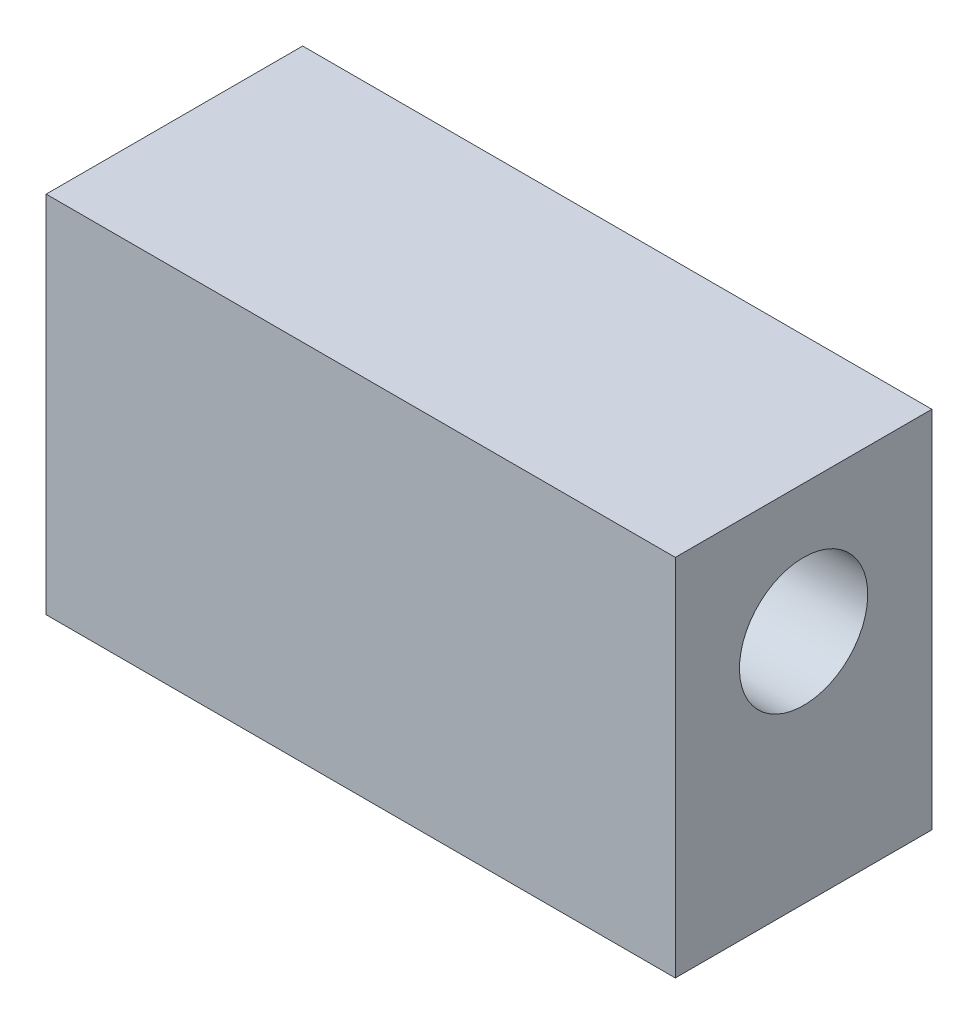
SolidWorks part; units mm, degrees
material "1060 Alloy"
ref_plane "Front" through (0, 0, 0) normal (0, 0, 1) x (1, 0, 0)
ref_plane "Top" through (0, 0, 0) normal (0, 1, 0) x (1, 0, 0)
ref_plane "Right" through (0, 0, 0) normal (1, 0, 0) x (0, 0, -1)
sketch "Sketch3" plane through (0, 0, 0) normal (0, 0, 1) x (1, 0, 0)
  line L0 (-0.127, -6.35) -> (30.1755, -6.35)
  line L1 (0, 0) -> (31.1484, 0)
  line L2 (0, 0) -> (0, -19.8376)
  line L3 (0, -19.8376) -> (31.1484, -19.8376)
  line L4 (31.1484, 0) -> (31.1484, -19.8376)
  line L5 (15.5742, -19.8376) -> (15.5742, 0) construction
  line L6 (15.5742, -6.35) -> (8.0621, -19.3614) construction
  line L15 (12.5496, -11.5887) -> (15.5742, -13.335) construction
  line L16 (15.5742, -6.35) -> (22.9274, -19.0862) construction
  circle A0 centre (15.5742, -6.35) radius 6.0492 construction
  point P14 (0, -6.35)
  point P17 (9.525, -6.35)
  point P19 (31.1484, -6.35)
  point P20 (7.7871, -19.8376)
  point P24 (23.3613, -19.8376)
  dimension "D2" = 6.35
  dimension "D6" = 3.4925
  dimension "D3" = 60
  dimension "D1" = 9.525
  dimension "D4" = 9.525
  dimension "D5" = 60
extrude "Boss-Extrude1" add sketch "Sketch3" along normal mid plane 12.7
sketch "Sketch4" plane through (0, 0, 0) normal (-1, 0, 0) x (0, 0, 1)
  circle A0 centre (0, -6.35) radius 3.175
  dimension "D1" = 6.35
extrude "Cut-Extrude1" cut sketch "Sketch4" against normal blind 9.525
ref_plane "Plane1" through (7.7871, -19.8376, 0) normal (-0.5, -0.866, 0) x (-0.866, 0.5, 0)
ref_plane "Mirror Plane" through (15.5742, 0, 0) normal (-1, 0, 0) x (0, 0, 1)
sketch "Sketch5" plane through (7.7871, -19.8376, 0) normal (-0.5, -0.866, 0) x (-0.866, 0.5, 0)
  circle A0 centre (0, 0) radius 3.175
  dimension "D1" = 6.35
extrude "Cut-Extrude5" cut sketch "Sketch5" against normal blind 9.525 and the other way up to next
sketch "Sketch6" plane through (0, 0, -6.35) normal (0, 0, -1) x (-1, 0, 0)
  circle A0 centre (-15.5742, -6.35) radius 3.175
  dimension "D1" = 6.35
extrude "Cut-Extrude6" cut sketch "Sketch6" against normal blind 9.525
mirror "Mirror1" about plane through (15.5742, 0, 0) normal (-1, 0, 0) of "Cut-Extrude1", "Cut-Extrude5"
sketch "Sketch8" plane through (31.1484, 0, 0) normal (1, 0, 0) x (0, 0, -1)
  line L0 (-6.35, -19.8376) -> (-6.35, 0) construction
  line L1 (-6.35, -18.034) -> (6.35, -18.034)
  line L2 (-6.35, -18.034) -> (-6.35, -19.8376)
  line L3 (-6.35, -19.8376) -> (6.35, -19.8376)
  line L4 (6.35, -18.034) -> (6.35, -19.8376)
  line L5 (-6.35, 0) -> (6.35, 0) construction
  dimension "D1" = 18.034
extrude "Cut-Extrude7" cut sketch "Sketch8" against normal through all
equation "\"truss_member_od\" = .25in"
equation "\"truss_member_id\"= 0in"
equation "\"truss_member_L1\" = 2.125in"
equation "\"connector_hole_depth\" = .375in"
equation "\"D1@Boss-Extrude1\"=\"truss_member_od\"*2"
equation "\"D6@Sketch3\"=\"truss_member_od\"/2*1.1"
equation "\"D1@Sketch4\"=\"truss_member_od\""
equation "\"D1@Cut-Extrude1\"=\"connector_hole_depth\""
equation "\"D1@Sketch3\"=\"connector_hole_depth\""
equation "\"D4@Sketch3\"=\"connector_hole_depth\""
equation "\"D1@Sketch5\"=\"truss_member_od\""
equation "\"D1@Cut-Extrude5\"=\"connector_hole_depth\""
equation "\"D1@Cut-Extrude6\"=\"connector_hole_depth\""
equation "\"D1@Sketch6\"=\"truss_member_od\""
